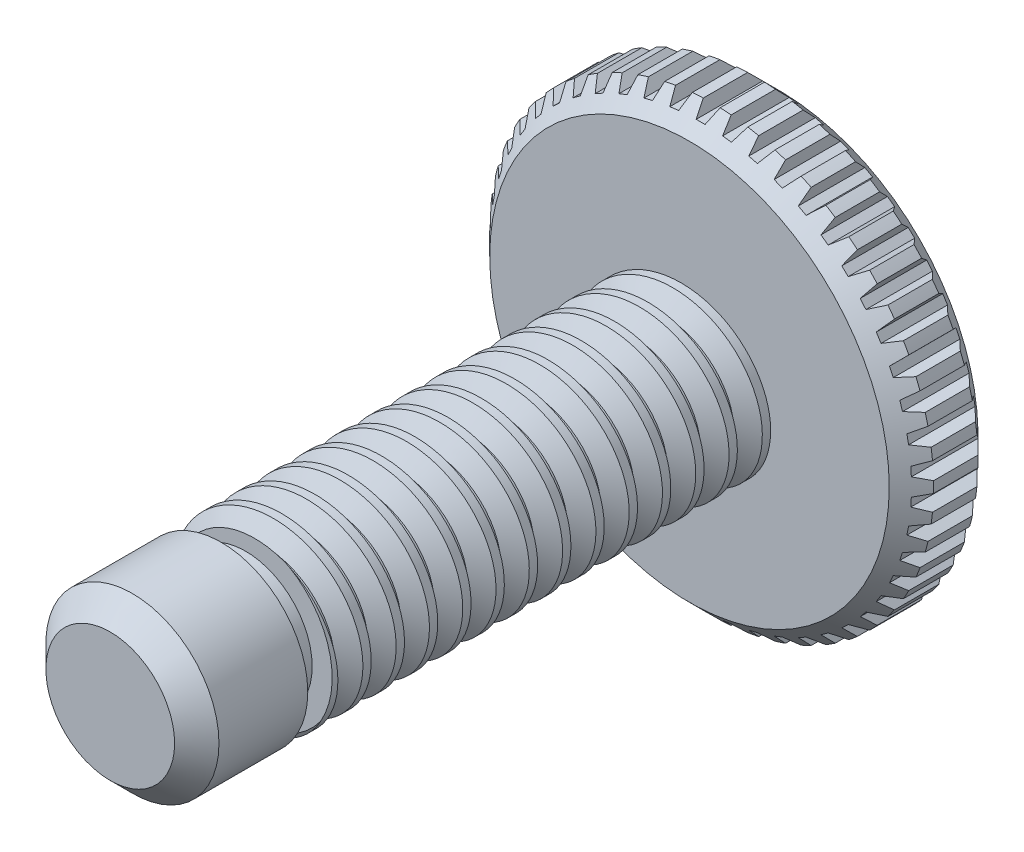
SolidWorks part; units mm, degrees
ref_plane "Front Plane" through (0, 0, 0) normal (0, 0, 1) x (1, 0, 0)
ref_plane "Top Plane" through (0, 0, 0) normal (0, 1, 0) x (1, 0, 0)
ref_plane "Right Plane" through (0, 0, 0) normal (1, 0, 0) x (0, 0, -1)
sketch "Sketch1" plane through (0, 0, 0) normal (0, 0, 1) x (1, 0, 0)
  circle A0 centre (0, 0) radius 3.9
extrude "Boss-Extrude1" add sketch "Sketch1" along normal blind 20
thread "Thread1" pitch 1.5 method cut profile "Thread Profile1" start angle 0, offset 2, length 25, pitch 1.5, diameter 7.8
ref_plane "Plane1" through (-3.9, 0, 22) normal (0, 1, 0) x (1, 0, 0)
sketch "Thread Profile1" plane through (-3.9, 0, 22) normal (0, 1, 0) x (1, 0, 0)
  line L0 (0, 0) -> (0, 1.5) construction
  line L1 (0, 0) -> (0.8119, 0.4687)
  line L2 (0.8119, 0.4687) -> (0.8119, 0.6562)
  line L3 (0.8119, 0.6562) -> (0, 1.125)
  line L4 (0.8119, 0.5625) -> (0, 0.5625) construction
  line L11 (0, 0) -> (0, 1.125)
  point P2 (0, 0)
  dimension "Pitch" = 1.5
  dimension "Profile_Angle" = 60
  dimension "Profile_Land" = 0.1875
  dimension "Profile_Height" = 0.8119
sketch "Sketch2" plane through (0, 0, 0) normal (0, 0, -1) x (-1, 0, 0)
  circle A0 centre (0, 0) radius 10
extrude "Boss-Extrude2" add sketch "Sketch2" along normal blind 4
sketch "Sketch3" plane through (0, 0, 20) normal (0, 0, 1) x (1, 0, 0)
  circle A0 centre (0, 0) radius 3
extrude "Boss-Extrude3" add sketch "Sketch3" along normal blind 1.1
sketch "Sketch4" plane through (0, 0, 21.1) normal (0, 0, 1) x (1, 0, 0)
  circle A0 centre (0, 0) radius 3.9
extrude "Boss-Extrude4" add sketch "Sketch4" along normal blind 5
chamfer "Chamfer1" distance 1 angle 45 2 edges at (-10, 0, 0) (-10, 0, -4)
sketch "Sketch5" plane through (0, 0, -4) normal (0, 0, -1) x (-1, 0, 0)
  line L0 (0, 9.2296) -> (0, -6.2018) construction
  line L2 (-0.2, 9.5) -> (0.2, 9.5)
  line L4 (-0.2, 9.5) -> (-0.3794, 9.9928)
  line L5 (0.2, 9.5) -> (0.3794, 9.9928)
  line L54 (1.3891, 9.4) -> (1.6288, 9.8665)
  line L55 (0.9922, 9.4502) -> (1.3891, 9.4)
  line L56 (0.9922, 9.4502) -> (0.8761, 9.9616)
  line L57 (2.5563, 9.1518) -> (2.8526, 9.5845)
  line L58 (2.1688, 9.2513) -> (2.5563, 9.1518)
  line L59 (2.1688, 9.2513) -> (2.1177, 9.7732)
  line L60 (3.6831, 8.7593) -> (4.0313, 9.1514)
  line L61 (3.3112, 8.9065) -> (3.6831, 8.7593)
  line L62 (3.3112, 8.9065) -> (3.3259, 9.4307)
  line L63 (4.7519, 8.2286) -> (5.1465, 8.574)
  line L64 (4.4014, 8.4213) -> (4.7519, 8.2286)
  line L65 (4.4014, 8.4213) -> (4.4816, 8.9395)
  line L66 (5.7458, 7.5681) -> (6.1805, 7.8614)
  line L67 (5.4222, 7.8032) -> (5.7458, 7.5681)
  line L68 (5.4222, 7.8032) -> (5.5667, 8.3073)
  line L69 (6.649, 6.7883) -> (7.1171, 7.0247)
  line L70 (6.3574, 7.0621) -> (6.649, 6.7883)
  line L71 (6.3574, 7.0621) -> (6.564, 7.5441)
  line L72 (7.4474, 5.9014) -> (7.9414, 6.0773)
  line L73 (7.1924, 6.2096) -> (7.4474, 5.9014)
  line L74 (7.1924, 6.2096) -> (7.4578, 6.662)
  line L75 (8.1283, 4.9215) -> (8.6405, 5.0341)
  line L76 (7.9139, 5.2592) -> (8.1283, 4.9215)
  line L77 (7.9139, 5.2592) -> (8.2339, 5.6747)
  line L78 (8.681, 3.8639) -> (9.2033, 3.9115)
  line L79 (8.5107, 4.2259) -> (8.681, 3.8639)
  line L80 (8.5107, 4.2259) -> (8.8802, 4.598)
  line L81 (9.0968, 2.7455) -> (9.6209, 2.7271)
  line L82 (8.9732, 3.1259) -> (9.0968, 2.7455)
  line L83 (8.9732, 3.1259) -> (9.3865, 3.4487)
  line L84 (9.3692, 1.5837) -> (9.8869, 1.4998)
  line L85 (9.2943, 1.9766) -> (9.3692, 1.5837)
  line L86 (9.2943, 1.9766) -> (9.7447, 2.2451)
  line L87 (9.4938, 0.3969) -> (9.9969, 0.2488)
  line L88 (9.4687, 0.7961) -> (9.4938, 0.3969)
  line L89 (9.4687, 0.7961) -> (9.9493, 1.0061)
  line L90 (9.4687, -0.7961) -> (9.9493, -1.0061)
  line L91 (9.4938, -0.3969) -> (9.4687, -0.7961)
  line L92 (9.4938, -0.3969) -> (9.9969, -0.2488)
  line L93 (9.2943, -1.9766) -> (9.7447, -2.2451)
  line L94 (9.3692, -1.5837) -> (9.2943, -1.9766)
  line L95 (9.3692, -1.5837) -> (9.8869, -1.4998)
  line L96 (8.9732, -3.1259) -> (9.3865, -3.4487)
  line L97 (9.0968, -2.7455) -> (8.9732, -3.1259)
  line L98 (9.0968, -2.7455) -> (9.6209, -2.7271)
  line L99 (8.5107, -4.2259) -> (8.8802, -4.598)
  line L100 (8.681, -3.8639) -> (8.5107, -4.2259)
  line L101 (8.681, -3.8639) -> (9.2033, -3.9115)
  line L102 (7.9139, -5.2592) -> (8.2339, -5.6747)
  line L103 (8.1283, -4.9215) -> (7.9139, -5.2592)
  line L104 (8.1283, -4.9215) -> (8.6405, -5.0341)
  line L105 (7.1924, -6.2096) -> (7.4578, -6.662)
  line L106 (7.4474, -5.9014) -> (7.1924, -6.2096)
  line L107 (7.4474, -5.9014) -> (7.9414, -6.0773)
  line L108 (6.3574, -7.0621) -> (6.564, -7.5441)
  line L109 (6.649, -6.7883) -> (6.3574, -7.0621)
  line L110 (6.649, -6.7883) -> (7.1171, -7.0247)
  line L111 (5.4222, -7.8032) -> (5.5667, -8.3073)
  line L112 (5.7458, -7.5681) -> (5.4222, -7.8032)
  line L113 (5.7458, -7.5681) -> (6.1805, -7.8614)
  line L114 (4.4014, -8.4213) -> (4.4816, -8.9395)
  line L115 (4.7519, -8.2286) -> (4.4014, -8.4213)
  line L116 (4.7519, -8.2286) -> (5.1465, -8.574)
  line L117 (3.3112, -8.9065) -> (3.3259, -9.4307)
  line L118 (3.6831, -8.7593) -> (3.3112, -8.9065)
  line L119 (3.6831, -8.7593) -> (4.0313, -9.1514)
  line L120 (2.1688, -9.2513) -> (2.1177, -9.7732)
  line L121 (2.5563, -9.1518) -> (2.1688, -9.2513)
  line L122 (2.5563, -9.1518) -> (2.8526, -9.5845)
  line L123 (0.9922, -9.4502) -> (0.8761, -9.9616)
  line L124 (1.3891, -9.4) -> (0.9922, -9.4502)
  line L125 (1.3891, -9.4) -> (1.6288, -9.8665)
  line L126 (-0.2, -9.5) -> (-0.3794, -9.9928)
  line L127 (0.2, -9.5) -> (-0.2, -9.5)
  line L128 (0.2, -9.5) -> (0.3794, -9.9928)
  line L129 (-1.3891, -9.4) -> (-1.6288, -9.8665)
  line L130 (-0.9922, -9.4502) -> (-1.3891, -9.4)
  line L131 (-0.9922, -9.4502) -> (-0.8761, -9.9616)
  line L132 (-2.5563, -9.1518) -> (-2.8526, -9.5845)
  line L133 (-2.1688, -9.2513) -> (-2.5563, -9.1518)
  line L134 (-2.1688, -9.2513) -> (-2.1177, -9.7732)
  line L135 (-3.6831, -8.7593) -> (-4.0313, -9.1514)
  line L136 (-3.3112, -8.9065) -> (-3.6831, -8.7593)
  line L137 (-3.3112, -8.9065) -> (-3.3259, -9.4307)
  line L138 (-4.7519, -8.2286) -> (-5.1465, -8.574)
  line L139 (-4.4014, -8.4213) -> (-4.7519, -8.2286)
  line L140 (-4.4014, -8.4213) -> (-4.4816, -8.9395)
  line L141 (-5.7458, -7.5681) -> (-6.1805, -7.8614)
  line L142 (-5.4222, -7.8032) -> (-5.7458, -7.5681)
  line L143 (-5.4222, -7.8032) -> (-5.5667, -8.3073)
  line L144 (-6.649, -6.7883) -> (-7.1171, -7.0247)
  line L145 (-6.3574, -7.0621) -> (-6.649, -6.7883)
  line L146 (-6.3574, -7.0621) -> (-6.564, -7.5441)
  line L147 (-7.4474, -5.9014) -> (-7.9414, -6.0773)
  line L148 (-7.1924, -6.2096) -> (-7.4474, -5.9014)
  line L149 (-7.1924, -6.2096) -> (-7.4578, -6.662)
  line L150 (-8.1283, -4.9215) -> (-8.6405, -5.0341)
  line L151 (-7.9139, -5.2592) -> (-8.1283, -4.9215)
  line L152 (-7.9139, -5.2592) -> (-8.2339, -5.6747)
  line L153 (-8.681, -3.8639) -> (-9.2033, -3.9115)
  line L154 (-8.5107, -4.2259) -> (-8.681, -3.8639)
  line L155 (-8.5107, -4.2259) -> (-8.8802, -4.598)
  line L156 (-9.0968, -2.7455) -> (-9.6209, -2.7271)
  line L157 (-8.9732, -3.1259) -> (-9.0968, -2.7455)
  line L158 (-8.9732, -3.1259) -> (-9.3865, -3.4487)
  line L159 (-9.3692, -1.5837) -> (-9.8869, -1.4998)
  line L160 (-9.2943, -1.9766) -> (-9.3692, -1.5837)
  line L161 (-9.2943, -1.9766) -> (-9.7447, -2.2451)
  line L162 (-9.4938, -0.3969) -> (-9.9969, -0.2488)
  line L163 (-9.4687, -0.7961) -> (-9.4938, -0.3969)
  line L164 (-9.4687, -0.7961) -> (-9.9493, -1.0061)
  line L165 (-9.4687, 0.7961) -> (-9.9493, 1.0061)
  line L166 (-9.4938, 0.3969) -> (-9.4687, 0.7961)
  line L167 (-9.4938, 0.3969) -> (-9.9969, 0.2488)
  line L168 (-9.2943, 1.9766) -> (-9.7447, 2.2451)
  line L169 (-9.3692, 1.5837) -> (-9.2943, 1.9766)
  line L170 (-9.3692, 1.5837) -> (-9.8869, 1.4998)
  line L171 (-8.9732, 3.1259) -> (-9.3865, 3.4487)
  line L172 (-9.0968, 2.7455) -> (-8.9732, 3.1259)
  line L173 (-9.0968, 2.7455) -> (-9.6209, 2.7271)
  line L174 (-8.5107, 4.2259) -> (-8.8802, 4.598)
  line L175 (-8.681, 3.8639) -> (-8.5107, 4.2259)
  line L176 (-8.681, 3.8639) -> (-9.2033, 3.9115)
  line L177 (-7.9139, 5.2592) -> (-8.2339, 5.6747)
  line L178 (-8.1283, 4.9215) -> (-7.9139, 5.2592)
  line L179 (-8.1283, 4.9215) -> (-8.6405, 5.0341)
  line L180 (-7.1924, 6.2096) -> (-7.4578, 6.662)
  line L181 (-7.4474, 5.9014) -> (-7.1924, 6.2096)
  line L182 (-7.4474, 5.9014) -> (-7.9414, 6.0773)
  line L183 (-6.3574, 7.0621) -> (-6.564, 7.5441)
  line L184 (-6.649, 6.7883) -> (-6.3574, 7.0621)
  line L185 (-6.649, 6.7883) -> (-7.1171, 7.0247)
  line L186 (-5.4222, 7.8032) -> (-5.5667, 8.3073)
  line L187 (-5.7458, 7.5681) -> (-5.4222, 7.8032)
  line L188 (-5.7458, 7.5681) -> (-6.1805, 7.8614)
  line L189 (-4.4014, 8.4213) -> (-4.4816, 8.9395)
  line L190 (-4.7519, 8.2286) -> (-4.4014, 8.4213)
  line L191 (-4.7519, 8.2286) -> (-5.1465, 8.574)
  line L192 (-3.3112, 8.9065) -> (-3.3259, 9.4307)
  line L193 (-3.6831, 8.7593) -> (-3.3112, 8.9065)
  line L194 (-3.6831, 8.7593) -> (-4.0313, 9.1514)
  line L195 (-2.1688, 9.2513) -> (-2.1177, 9.7732)
  line L196 (-2.5563, 9.1518) -> (-2.1688, 9.2513)
  line L197 (-2.5563, 9.1518) -> (-2.8526, 9.5845)
  line L198 (-0.9922, 9.4502) -> (-0.8761, 9.9616)
  line L199 (-1.3891, 9.4) -> (-0.9922, 9.4502)
  line L200 (-1.3891, 9.4) -> (-1.6288, 9.8665)
  arc A0 (0.8761, 9.9616) -> (1.6288, 9.8665) centre (0.9523, 7.5383) cw
  circle A2 centre (0, 0) radius 10 construction
  arc A3 (-0.3794, 9.9928) -> (0.3794, 9.9928) centre (0, 7.5982) cw
  arc A20 (2.1177, 9.7732) -> (2.8526, 9.5845) centre (1.8896, 7.3595) cw
  arc A21 (3.3259, 9.4307) -> (4.0313, 9.1514) centre (2.7971, 7.0646) cw
  arc A22 (4.4816, 8.9395) -> (5.1465, 8.574) centre (3.6605, 6.6584) cw
  arc A23 (5.5667, 8.3073) -> (6.1805, 7.8614) centre (4.4661, 6.1471) cw
  arc A24 (6.564, 7.5441) -> (7.1171, 7.0247) centre (5.2013, 5.5388) cw
  arc A25 (7.4578, 6.662) -> (7.9414, 6.0773) centre (5.8545, 4.8433) cw
  arc A26 (8.2339, 5.6747) -> (8.6405, 5.0341) centre (6.4154, 4.0713) cw
  arc A27 (8.8802, 4.598) -> (9.2033, 3.9115) centre (6.8751, 3.2352) cw
  arc A28 (9.3865, 3.4487) -> (9.6209, 2.7271) centre (7.2263, 2.348) cw
  arc A29 (9.7447, 2.2451) -> (9.8869, 1.4998) centre (7.4636, 1.4238) cw
  arc A30 (9.9493, 1.0061) -> (9.9969, 0.2488) centre (7.5832, 0.4771) cw
  arc A31 (9.9969, -0.2488) -> (9.9493, -1.0061) centre (7.5832, -0.4771) cw
  arc A32 (9.8869, -1.4998) -> (9.7447, -2.2451) centre (7.4636, -1.4238) cw
  arc A33 (9.6209, -2.7271) -> (9.3865, -3.4487) centre (7.2263, -2.348) cw
  arc A34 (9.2033, -3.9115) -> (8.8802, -4.598) centre (6.8751, -3.2352) cw
  arc A35 (8.6405, -5.0341) -> (8.2339, -5.6747) centre (6.4154, -4.0713) cw
  arc A36 (7.9414, -6.0773) -> (7.4578, -6.662) centre (5.8545, -4.8433) cw
  arc A37 (7.1171, -7.0247) -> (6.564, -7.5441) centre (5.2013, -5.5388) cw
  arc A38 (6.1805, -7.8614) -> (5.5667, -8.3073) centre (4.4661, -6.1471) cw
  arc A39 (5.1465, -8.574) -> (4.4816, -8.9395) centre (3.6605, -6.6584) cw
  arc A40 (4.0313, -9.1514) -> (3.3259, -9.4307) centre (2.7971, -7.0646) cw
  arc A41 (2.8526, -9.5845) -> (2.1177, -9.7732) centre (1.8896, -7.3595) cw
  arc A42 (1.6288, -9.8665) -> (0.8761, -9.9616) centre (0.9523, -7.5383) cw
  arc A43 (0.3794, -9.9928) -> (-0.3794, -9.9928) centre (0, -7.5982) cw
  arc A44 (-0.8761, -9.9616) -> (-1.6288, -9.8665) centre (-0.9523, -7.5383) cw
  arc A45 (-2.1177, -9.7732) -> (-2.8526, -9.5845) centre (-1.8896, -7.3595) cw
  arc A46 (-3.3259, -9.4307) -> (-4.0313, -9.1514) centre (-2.7971, -7.0646) cw
  arc A47 (-4.4816, -8.9395) -> (-5.1465, -8.574) centre (-3.6605, -6.6584) cw
  arc A48 (-5.5667, -8.3073) -> (-6.1805, -7.8614) centre (-4.4661, -6.1471) cw
  arc A49 (-6.564, -7.5441) -> (-7.1171, -7.0247) centre (-5.2013, -5.5388) cw
  arc A50 (-7.4578, -6.662) -> (-7.9414, -6.0773) centre (-5.8545, -4.8433) cw
  arc A51 (-8.2339, -5.6747) -> (-8.6405, -5.0341) centre (-6.4154, -4.0713) cw
  arc A52 (-8.8802, -4.598) -> (-9.2033, -3.9115) centre (-6.8751, -3.2352) cw
  arc A53 (-9.3865, -3.4487) -> (-9.6209, -2.7271) centre (-7.2263, -2.348) cw
  arc A54 (-9.7447, -2.2451) -> (-9.8869, -1.4998) centre (-7.4636, -1.4238) cw
  arc A55 (-9.9493, -1.0061) -> (-9.9969, -0.2488) centre (-7.5832, -0.4771) cw
  arc A56 (-9.9969, 0.2488) -> (-9.9493, 1.0061) centre (-7.5832, 0.4771) cw
  arc A57 (-9.8869, 1.4998) -> (-9.7447, 2.2451) centre (-7.4636, 1.4238) cw
  arc A58 (-9.6209, 2.7271) -> (-9.3865, 3.4487) centre (-7.2263, 2.348) cw
  arc A59 (-9.2033, 3.9115) -> (-8.8802, 4.598) centre (-6.8751, 3.2352) cw
  arc A60 (-8.6405, 5.0341) -> (-8.2339, 5.6747) centre (-6.4154, 4.0713) cw
  arc A61 (-7.9414, 6.0773) -> (-7.4578, 6.662) centre (-5.8545, 4.8433) cw
  arc A62 (-7.1171, 7.0247) -> (-6.564, 7.5441) centre (-5.2013, 5.5388) cw
  arc A63 (-6.1805, 7.8614) -> (-5.5667, 8.3073) centre (-4.4661, 6.1471) cw
  arc A64 (-5.1465, 8.574) -> (-4.4816, 8.9395) centre (-3.6605, 6.6584) cw
  arc A65 (-4.0313, 9.1514) -> (-3.3259, 9.4307) centre (-2.7971, 7.0646) cw
  arc A66 (-2.8526, 9.5845) -> (-2.1177, 9.7732) centre (-1.8896, 7.3595) cw
  arc A67 (-1.6288, 9.8665) -> (-0.8761, 9.9616) centre (-0.9523, 7.5383) cw
  point P92 (0, 0)
  point P259 (0, 0)
  dimension "D1" = 0.2
  dimension "D2" = 0.2
  dimension "D3" = 110
  dimension "D4" = 9.5
  dimension "D5" = 110
  dimension "D6" = 50
extrude "Cut-Extrude1" cut sketch "Sketch5" against normal blind 5
chamfer "Chamfer2" distance 1 angle 45 1 edges at (3.9, 0, 26.1)
